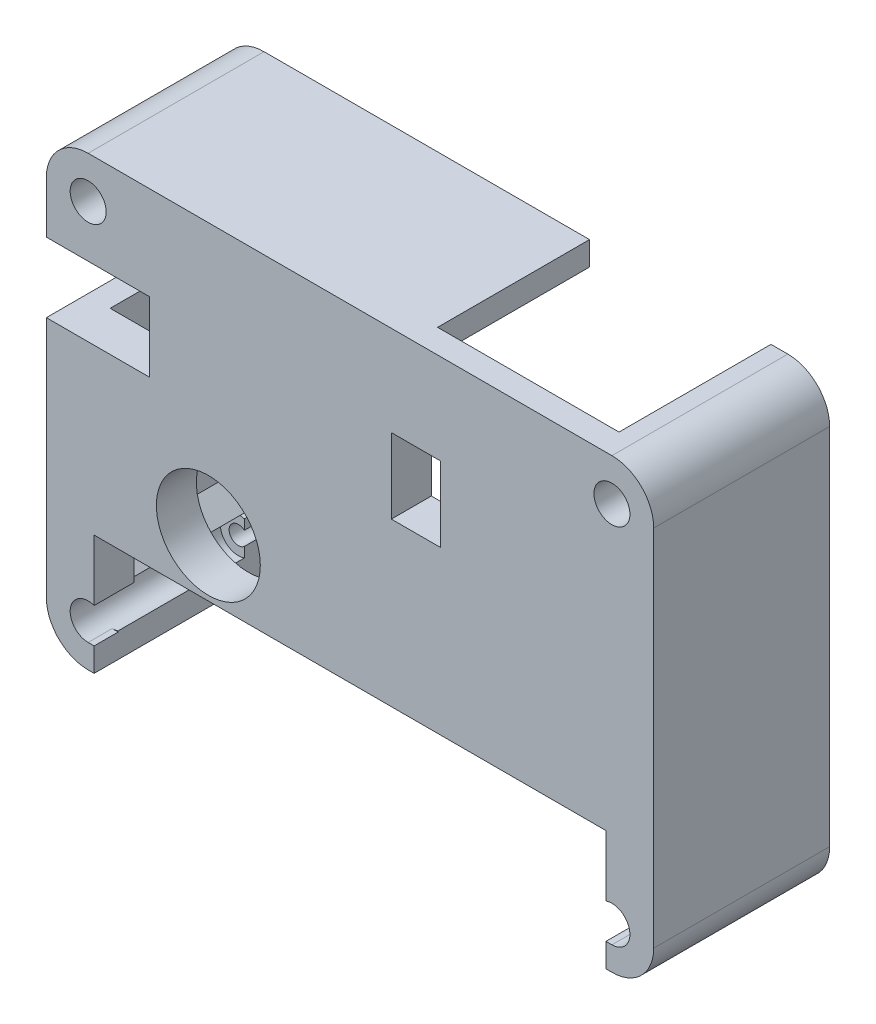
SolidWorks part; units mm, degrees
note: The reader was unsure of these and kept them because the rebuilt part matched: shared geometry of "Sketch1<6>", "Sketch2<5>", "Sketch2<6>".
ref_plane "Front Plane" through (0, 0, 0) normal (0, 0, 1) x (1, 0, 0)
ref_plane "Top Plane" through (0, 0, 0) normal (0, 1, 0) x (1, 0, 0)
ref_plane "Right Plane" through (0, 0, 0) normal (1, 0, 0) x (0, 0, -1)
sketch "Sketch1" plane through (0, 0, 0) normal (0, 0, 1) x (1, 0, 0)
  line L0 (35, -25) -> (35, 0) construction
  line L1 (0, 0) -> (70, 0) construction
  line L2 (0, 0) -> (0, -50) construction
  line L3 (0, -50) -> (70, -50) construction
  line L4 (70, 0) -> (70, -50) construction
  line L5 (0, 0) -> (70, -50) construction
  line L6 (0, -50) -> (70, 0) construction
  line L7 (70, -25) -> (0, -25) construction
  line L8 (63.031, -50) -> (70, -43.031)
  line L9 (63.031, 0) -> (70, -6.969)
  line L10 (6.969, 0) -> (0, -6.969)
  line L11 (6.969, -50) -> (0, -43.031)
  circle A0 centre (2.25, -2.25) radius 1.15
  circle A2 centre (2.25, -2.25) radius 2.25
  circle A3 centre (2.25, -47.75) radius 2.25
  circle A4 centre (2.25, -47.75) radius 1.15
  circle A5 centre (67.75, -47.75) radius 1.15
  circle A6 centre (67.75, -47.75) radius 2.25
  circle A7 centre (67.75, -2.25) radius 2.25
  circle A8 centre (67.75, -2.25) radius 1.15
  circle A9 centre (67.75, -47.75) radius 5.228
  circle A10 centre (67.75, -2.25) radius 5.228
  circle A11 centre (2.25, -2.25) radius 5.228
  circle A12 centre (2.25, -47.75) radius 5.228
  point P4 (35, -25)
  dimension "D3" = 4.5
  dimension "D4" = 2.3
  dimension "D1" = 70
  dimension "D2" = 50
extrude "Boss-Extrude4" add sketch "Sketch1" along normal blind 3.22 contours L10 A2 | L10 A2 A0 | A3 L11 A4 | A3 L11 | L8 A6 A5 | L8 A6 | A7 L9 A8 | A7 L9
extrude "Boss-Extrude5" add sketch "Sketch1<6>" along normal blind 19 contours A10 L9 A7 | L10 A11 A2 | A12 L11 A3 | L8 A9 A6
sketch "Sketch1<6>" plane through (0, 0, 0) normal (0, 0, 1) x (1, 0, 0) same geometry as "Sketch1"
sketch "Sketch2" plane through (0, 0, 19) normal (0, 0, 1) x (1, 0, 0)
  line L0 (0, -2.25) -> (0, -47.75)
  line L1 (35, 2.978) -> (35, -52.978) construction
  line L2 (-2.978, 2.978) -> (72.978, 2.978)
  line L3 (-2.978, 2.978) -> (-2.978, -52.978)
  line L4 (-2.978, -52.978) -> (72.978, -52.978)
  line L5 (72.978, 2.978) -> (72.978, -52.978)
  line L6 (-2.978, 2.978) -> (72.978, -52.978) construction
  line L7 (-2.978, -52.978) -> (72.978, 2.978) construction
  line L8 (72.978, -25) -> (-2.978, -25) construction
  line L9 (70, -2.25) -> (70, -47.75)
  line L10 (2.25, 0) -> (67.75, 0)
  line L11 (2.25, -50) -> (67.75, -50)
  line L12 (0, -2.25) -> (-2.978, -2.25)
  line L13 (2.25, 0) -> (2.25, 2.978)
  line L14 (2.25, -50) -> (2.25, -52.978)
  line L15 (0, -47.75) -> (-2.978, -47.75)
  line L16 (70, -47.75) -> (72.978, -47.75)
  line L17 (67.75, -50) -> (67.75, -52.978)
  line L18 (70, -2.25) -> (72.978, -2.25)
  line L19 (67.75, 0) -> (67.75, 2.978)
  line L21 (3, -38) -> (67, -38)
  line L22 (3, -38) -> (3, -52.978)
  line L23 (3, -52.978) -> (67, -52.978)
  line L24 (67, -38) -> (67, -52.978)
  line L25 (3, -38) -> (67, -52.978) construction
  line L26 (3, -52.978) -> (67, -38) construction
  line L27 (40.17, -8.315) -> (46.29, -8.315)
  line L28 (40.17, -8.315) -> (40.17, -17.685)
  line L29 (40.17, -17.685) -> (46.29, -17.685)
  line L30 (46.29, -8.315) -> (46.29, -17.685)
  line L31 (40.17, -8.315) -> (46.29, -17.685) construction
  line L32 (40.17, -17.685) -> (46.29, -8.315) construction
  arc A0 (4.4881, -2.4809) -> (2.4809, -4.4881) centre (2.25, -2.25) ccw construction
  arc A1 (2.4809, -45.5119) -> (4.4881, -47.5191) centre (2.25, -47.75) ccw construction
  circle A2 centre (2.25, -47.75) radius 5.228
  circle A3 centre (67.75, -47.75) radius 5.228
  circle A4 centre (67.75, -2.25) radius 5.228
  circle A5 centre (2.25, -2.25) radius 2.25
  arc A6 (6.969, 0) -> (0, -6.969) centre (2.25, -2.25) ccw construction
  arc A7 (0, -43.031) -> (6.969, -50) centre (2.25, -47.75) ccw construction
  arc A8 (63.031, -50) -> (70, -43.031) centre (67.75, -47.75) ccw construction
  circle A9 centre (2.25, -47.75) radius 2.25
  arc A10 (67.5191, -4.4881) -> (65.5119, -2.4809) centre (67.75, -2.25) ccw construction
  circle A11 centre (2.25, -2.25) radius 5.228
  circle A12 centre (2.25, -47.75) radius 2.25
  circle A13 centre (67.75, -47.75) radius 2.25
  circle A14 centre (67.75, -2.25) radius 2.25
  circle A15 centre (17.28, -30.89) radius 6.5
  point P13 (35, -25)
  point P58 (35, -45.489)
  point P65 (43.23, -13)
  line M9 (4.4881, -2.4809) -> (6.969, 0)
  arc M10 (6.969, 0) -> (0, -6.969) centre (2.25, -2.25) ccw
  line M11 (0, -6.969) -> (2.4809, -4.4881)
  arc M12 (2.4809, -4.4881) -> (4.4881, -2.4809) centre (2.25, -2.25) cw
  dimension "D3" = 13
  dimension "D1" = 64
  dimension "D2" = 12
  dimension "D4" = 17.28
  dimension "D5" = 19.11
  dimension "D6" = 6.12
  dimension "D7" = 9.37
  dimension "D8" = 13
  dimension "D9" = 26.77
extrude "Boss-Extrude6" add sketch "Sketch2" against normal blind 19 contours L15 L0 L3 M10 | L10 L19 L2 M10 | L18 L9 L16 L5 | L17 L11 L14 L4 | L11 A2 L4 L22 | A3 L11 L24 L4
sketch "Sketch3" plane through (0, 0, 0) normal (1, 0, 0) x (0, 0, -1)
  line L0 (0, -2.25) -> (0, -47.75) construction
  line L1 (0, -8.72) -> (-19, -8.72)
  line L2 (0, -8.72) -> (0, -17.44)
  line L3 (0, -17.44) -> (-19, -17.44)
  line L4 (-19, -8.72) -> (-19, -17.44)
  line L5 (0, -8.72) -> (-19, -17.44) construction
  line L6 (0, -17.44) -> (-19, -8.72) construction
  line L7 (-19, -2.25) -> (-19, -47.75) construction
  point P4 (-9.5, -13.08)
  dimension "D1" = 8.72
  dimension "D2" = 8.72
extrude "Cut-Extrude1" cut sketch "Sketch3" against normal through all
sketch "Sketch4" plane through (0, 0, 0) normal (0, -1, 0) x (1, 0, 0)
  line L0 (2.25, 19) -> (67.75, 19) construction
  line L1 (0, 0) -> (70, 0)
  line L2 (0, 0) -> (0, 19)
  line L3 (0, 19) -> (70, 19)
  line L4 (70, 0) -> (70, 19)
  line L5 (0, 0) -> (70, 19) construction
  line L6 (0, 19) -> (70, 0) construction
  line L8 (65.64, 0) -> (42.95, 0)
  line L9 (65.64, 0) -> (65.64, 19)
  line L10 (65.64, 19) -> (42.95, 19)
  line L11 (42.95, 0) -> (42.95, 19)
  line L12 (65.64, 0) -> (42.95, 19) construction
  line L13 (65.64, 19) -> (42.95, 0) construction
  point P4 (35, 9.5)
  point P12 (54.295, 9.5)
  dimension "D1" = 70
  dimension "D2" = 4.36
  dimension "D3" = 22.69
extrude "Boss-Extrude9" add sketch "Sketch2<5>" along normal blind 3 and the other way blind 2 contours A11 L0 A2 L11 L22 L21 L24 A3 L9 A4 L10 | A2 L15 L0 | L14 A9 L15 A2 | A2 L11 L14 | L11 A2 L4 L22 | A3 L11 L24 L4 | L11 A3 L17 | A13 L17 A3 L16 | L16 A3 L9 | L5 A4 L9 A3 | A4 L18 L9 | L19 A14 L18 A4 | A4 L10 L19 | L10 A4 L2 M10 | L13 L12 M12 M10 | L0 L12 M10 | L3 A2 L0 M10 | A11 A5 M11 M9 | L10 M12 M9 | L13 L10 M10 | L0 M12 M11 | L9 A14 L10 A4 | L0 A9 L22 A2 | A13 L9 A3 L24
sketch "Sketch2<5>" plane through (0, 0, 19) normal (0, 0, 1) x (1, 0, 0) same geometry as "Sketch2"
extrude "Cut-Extrude8" cut sketch "Sketch2<6>" against normal up to next and the other way up to next contours L21 L24 L23 L22
sketch "Sketch2<6>" plane through (0, 0, 19) normal (0, 0, 1) x (1, 0, 0) same geometry as "Sketch2"
extrude "Cut-Extrude10" cut sketch "Sketch4" against normal up to next and the other way blind 3 contours L11 L10 L9 L8
sketch "Sketch5" plane through (0, 0, 17) normal (0, 0, -1) x (-1, 0, 0)
  line L1 (2.978, -8.72) -> (-9.9162, -8.72)
  line L2 (2.978, -8.72) -> (2.978, -17.44)
  line L3 (2.978, -17.44) -> (-9.9162, -17.44)
  line L4 (-9.9162, -8.72) -> (-9.9162, -17.44)
  line L5 (2.978, -8.72) -> (-9.9162, -17.44) construction
  line L6 (2.978, -17.44) -> (-9.9162, -8.72) construction
  point P4 (-3.4691, -13.08)
  point P6 (0, 0)
extrude "Cut-Extrude11" cut sketch "Sketch5" against normal up to next
